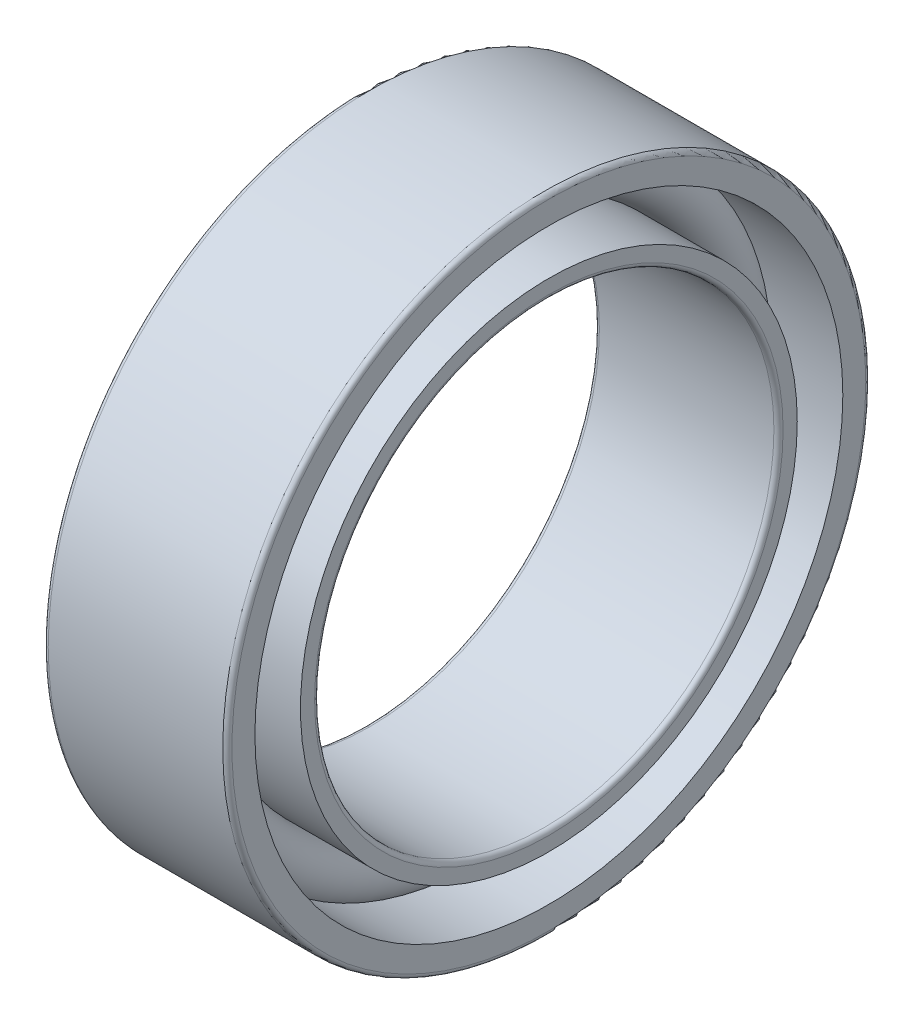
SolidWorks part; units mm, degrees
ref_plane "Plane1" through (0, 0, 0) normal (0, 0, 1) x (1, 0, 0)
ref_plane "Plane2" through (0, 0, 0) normal (0, 1, 0) x (1, 0, 0)
ref_plane "Plane3" through (0, 0, 0) normal (1, 0, 0) x (0, 0, -1)
sketch "Clipboard" plane through (0, 0, 0) normal (0, 0, 1) x (1, 0, 0)
  line L0 (-10, 0) -> (10, 0) construction
  line L1 (0, 0) -> (22.3471, -0.7804)
  line L2 (0, 0) -> (17.989, 0.6282)
  line L3 (0, 0) -> (22.3471, -0.7804)
  line L4 (0, 0) -> (-22.3573, -0.3902)
  dimension "BallCLRad" = 18
sketch "CagSpiSke" plane through (0, 0, 0) normal (0, 0, 1) x (1, 0, 0)
  line L0 (0.45, 17.7) -> (0.45, 18.3)
  line L1 (0.45, 18.3) -> (-0.45, 18.3)
  line L2 (-0.45, 18.3) -> (-0.45, 17.7)
  line L3 (-0.45, 17.7) -> (0.45, 17.7)
  line L4 (-20.6375, 0) -> (20.6375, 0) construction
  line L5 (0, 0) -> (0, 23.7692) construction
  dimension "OD" = 36.6
  dimension "ID" = 35.4
revolve "CageSpine" add sketch "CagSpiSke" angle 0.001 about L4
ref_axis "Axis1" through (-50, 0, 0) along (1, 0, 0)
sketch "CagBalSke" plane through (0, 0, 0) normal (0, 0, 1) x (1, 0, 0)
  line L0 (-1.98, 18) -> (1.98, 18)
  line L1 (-1.905, 18) -> (1.905, 18) construction
  line L2 (-10, 0) -> (10, 0) construction
  line L3 (0, 0) -> (0, 24) construction
  arc A0 (1.98, 18) -> (-1.98, 18) centre (0, 18) cw
  dimension "BallCLRad" = 18
revolve "CageBall" [suppressed] add sketch "CagBalSke" angle 360 about L1 reverse direction yes
pattern_circular "CageBalls" [suppressed] count 2 every 180 about axis through (-50, 0, 0) along (1, 0, 0)
sketch "CagTrmODSke" plane through (0, 0, 0) normal (0, 0, 1) x (1, 0, 0)
  line L0 (1.981, 18.3) -> (1.981, 19.981)
  line L1 (1.981, 19.981) -> (-1.981, 19.981)
  line L2 (-1.981, 19.981) -> (-1.981, 18.3)
  line L3 (-1.981, 18.3) -> (1.981, 18.3)
  line L4 (-20.6375, 0) -> (20.6375, 0) construction
  line L5 (0, 0) -> (0, 25) construction
  dimension "Width" = 3.962
  dimension "ID" = 36.6
  dimension "OD" = 39.962
revolve "CageTrimOD" [suppressed] cut sketch "CagTrmODSke" angle 360 about L4 reverse direction yes
sketch "CagTrmIDSke" plane through (0, 0, 0) normal (0, 0, 1) x (1, 0, 0)
  line L0 (1.981, 16.021) -> (1.981, 17.7)
  line L1 (1.981, 17.7) -> (-1.981, 17.7)
  line L2 (-1.981, 17.7) -> (-1.981, 16.021)
  line L3 (-1.981, 16.021) -> (1.981, 16.021)
  line L4 (-20.6375, 0) -> (20.6375, 0) construction
  line L5 (0, 0) -> (0, 25) construction
  dimension "Width" = 3.962
  dimension "ID" = 32.042
  dimension "OD" = 35.4
revolve "CageTrimID" [suppressed] cut sketch "CagTrmIDSke" angle 360 about L4 reverse direction yes
sketch "BalSimSke" plane through (0, 0, 0) normal (0, 0, 1) x (1, 0, 0)
  line L0 (-10, 0) -> (10, 0) construction
  line L1 (-10, 18) -> (10, 18) construction
  line L2 (0, 0) -> (0, 23) construction
  circle A0 centre (0, 18) radius 1.8
  dimension "BallCLRad" = 18
  dimension "Ball_diameter" = 3.6
revolve "BallsSimplified" add sketch "BalSimSke" angle 360 about L0
sketch "BalDetSke" plane through (0, 0, 0) normal (0, 0, 1) x (1, 0, 0)
  line L0 (-1.8, 18) -> (1.8, 18)
  line L1 (-1.905, 18) -> (1.905, 18) construction
  line L2 (0, 0) -> (0, 25) construction
  arc A0 (1.8, 18) -> (-1.8, 18) centre (0, 18) cw
  dimension "BallCLRad" = 18
  dimension "Ball_diameter" = 3.6
revolve "BallDetailed" [suppressed] add sketch "BalDetSke" angle 360 about L1 reverse direction yes
sketch "InnRacSke" plane through (0, 0, 0) normal (0, 0, 1) x (1, 0, 0)
  line L0 (-1.3079, 16.8) -> (-6, 16.8)
  line L1 (-6, 16.8) -> (-6, 15.3)
  line L2 (-5.7, 15) -> (5.7, 15)
  line L3 (6, 15.3) -> (6, 16.225)
  line L4 (0, 16.225) -> (6, 16.225)
  line L5 (-20.6375, 0) -> (20.6375, 0) construction
  line L6 (0, 0) -> (0, 30) construction
  arc A0 (-6, 15.3) -> (-5.7, 15) centre (-5.7, 15.3) ccw
  arc A1 (5.7, 15) -> (6, 15.3) centre (5.7, 15.3) ccw
  arc A2 (0, 16.225) -> (-1.3079, 16.8) centre (0, 18) cw
  dimension "BallCLRad" = 18
  dimension "Fillet_radius" = 0.3
  dimension "Ball_diameter" = 3.55
  dimension "ID" = 30
  dimension "OD" = 33.6
  dimension "Width" = 12
revolve "InnerRace" add sketch "InnRacSke" angle 360 about L5 reverse direction yes
sketch "OutRacSke" plane through (0, 0, 0) normal (0, 0, 1) x (1, 0, 0)
  line L0 (0, 19.775) -> (-6, 19.775)
  line L1 (-6, 19.775) -> (-6, 20.7)
  line L2 (-5.7, 21) -> (5.7, 21)
  line L3 (6, 20.7) -> (6, 19.2)
  line L4 (6, 19.2) -> (1.3079, 19.2)
  line L5 (-20.6375, 0) -> (20.6375, 0) construction
  line L6 (0, 0) -> (0, 30) construction
  arc A0 (-6, 20.7) -> (-5.7, 21) centre (-5.7, 20.7) cw
  arc A1 (5.7, 21) -> (6, 20.7) centre (5.7, 20.7) cw
  arc A2 (1.3079, 19.2) -> (0, 19.775) centre (0, 18) ccw
  dimension "BallCLRad" = 18
  dimension "Fillet_radius" = 0.3
  dimension "Ball_diameter" = 3.55
  dimension "Width" = 12
revolve "OuterRace" add sketch "OutRacSke" angle 360 about L5 reverse direction yes
pattern_circular "BallsDetailed" [suppressed] count 2 every 180 about axis through (-50, 0, 0) along (1, 0, 0)
equation "\"BallCLRad@Clipboard\" = ( \"OD@OutRacSke\" + \"ID@InnRacSke\" ) / 4"
equation "\"BallCLRad@BalSimSke\" = \"BallCLRad@Clipboard\""
equation "\"BallCLRad@BalDetSke\" = \"BallCLRad@Clipboard\""
equation "\"BallCLRad@InnRacSke\" = \"BallCLRad@Clipboard\""
equation "\"BallCLRad@OutRacSke\" = \"BallCLRad@Clipboard\""
equation "\"Ball_diameter@InnRacSke\" = \"Ball_diameter@BalDetSke\" - 0.05"
equation "\"Ball_diameter@OutRacSke\" = \"Ball_diameter@BalDetSke\" - 0.05"
equation "\"Ball_diameter@BalSimSke\" = \"Ball_diameter@BalDetSke\""
equation "\"Width@OutRacSke\" = \"Width@InnRacSke\""
equation "\"Fillet_radius@OutRacSke\" = \"Fillet_radius@InnRacSke\""
equation "\"Max_count@Clipboard\" = int( 3.14159265 / atn(( \"Ball_diameter@BalDetSke\" / 2) / sqr( \"BallCLRad@Clipboard\"  *  \"BallCLRad@Clipboard\" - ( \"Ball_diameter@BalDetSke\" / 2) *  ( \"Ball_diameter@BalDetSke\" / 2))))"
equation "\"Max_count@Clipboard\" = ((sgn( \"Max_count@Clipboard\" - \"Count@Clipboard\" )-1)*( \"Max_count@Clipboard\" - \"Count@Clipboard\" ))/-2+ \"Count@Clipboard\""
equation "\"Count@BallsDetailed\" = int( \"Show_count@Clipboard\" ) "
equation "\"Count@BallsDetailed\" = ((sgn( \"Count@BallsDetailed\" - \"Max_count@Clipboard\" )-1)*( \"Count@BallsDetailed\" - \"Max_count@Clipboard\" ))/-2+ \"Max_count@Clipboard\""
equation "\"Count@BallsDetailed\" = ((sgn( \"Count@BallsDetailed\" - \"Min_count@Clipboard\" )+1)*( \"Count@BallsDetailed\" - \"Min_count@Clipboard\"))/2 +\"Min_count@Clipboard\""
equation "\"Angle@BallsDetailed\" = 360.0 / \"Max_count@Clipboard\""
equation "\"BallCLRad@CagBalSke\" = \"BallCLRad@Clipboard\""
equation "\"Count@CageBalls\" = \"Count@BallsDetailed\""
equation "\"Angle@CageBalls\" = \"Angle@BallsDetailed\""
equation "\"Angle@CageSpine\" =  \"Angle@CageBalls\" * ( \"Count@CageBalls\" -1 + int( \"Count@CageBalls\" / \"Max_count@Clipboard\" ) )  + 0.001 -  int( \"Count@CageBalls\" / \"Max_count@Clipboard\" ) * 0.001"
equation "\"Angle@CageSpine\" =  \"Angle@CageSpine\" * int( \"Min_count@Clipboard\" / 2) + int(1 / \"Min_count@Clipboard\")  * 0.001"
equation "\"CageWallOD@CagBalSke\" =  \"Ball_diameter@BalDetSke\" * 1.1"
equation "\"Thickness@CagSpiSke\" =  \"Ball_diameter@BalDetSke\" * 0.25"
equation "\"OD@CagTrmODSke\" = \"BallCLRad@Clipboard\" * 2 + \"CageWallOD@CagBalSke\" + 0.002"
equation "\"ID@CagTrmODSke\" = \"BallCLRad@Clipboard\" * 2 + \"Ball_diameter@BalDetSke\" / 6"
equation "\"OD@CagTrmIDSke\" = \"BallCLRad@Clipboard\" * 2 - \"Ball_diameter@BalDetSke\" / 6"
equation "\"ID@CagTrmIDSke\" = \"BallCLRad@Clipboard\" * 2 - \"CageWallOD@CagBalSke\" + 0.002"
equation "\"OD@CagSpiSke\" = \"ID@CagTrmODSke\""
equation "\"ID@CagSpiSke\" = \"OD@CagTrmIDSke\""
equation "\"Width@CagTrmODSke\" = \"CageWallOD@CagBalSke\" + 0.002"
equation "\"Width@CagTrmIDSke\" = \"CageWallOD@CagBalSke\" + 0.002"
